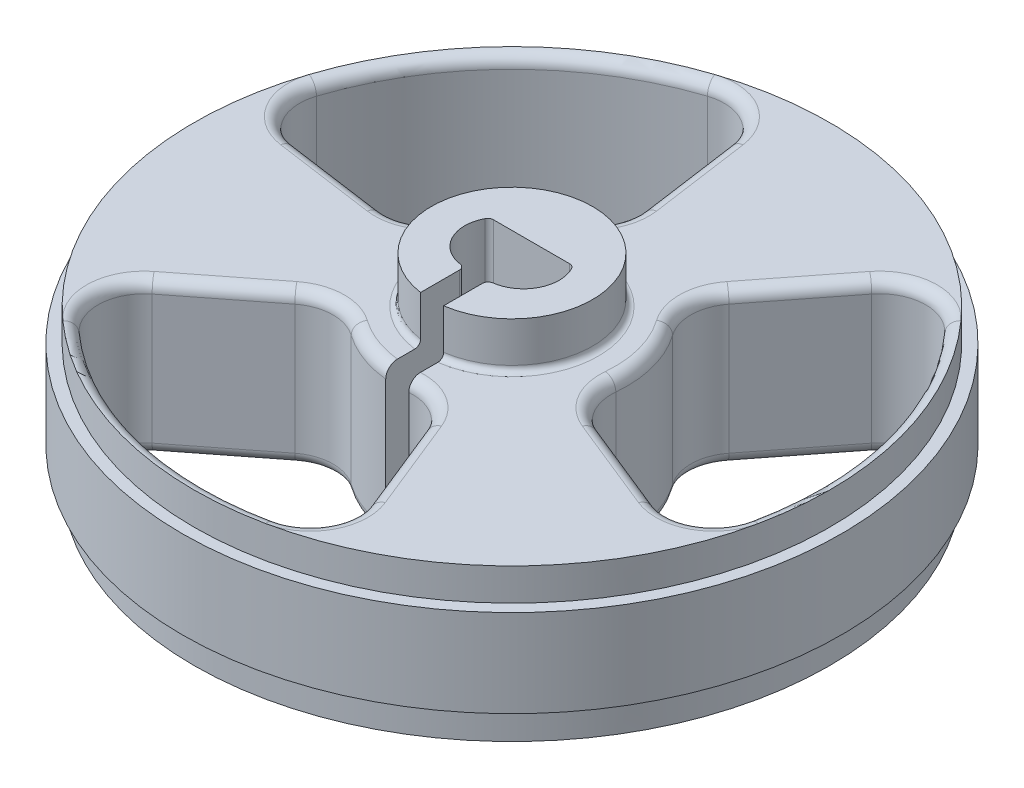
SolidWorks part; units mm, degrees
material "Nylon 101"
ref_plane "Front" through (0, 0, 0) normal (0, 0, 1) x (1, 0, 0)
ref_plane "Top" through (0, 0, 0) normal (0, 1, 0) x (1, 0, 0)
ref_plane "Right" through (0, 0, 0) normal (1, 0, 0) x (0, 0, -1)
sketch "Sketch1" plane through (0, 0, 0) normal (1, 0, 0) x (0, 0, -1)
  line L0 (0, 7.6229) -> (0, -6.4854) construction
  line L1 (0, -4.3) -> (13.8, -4.3)
  line L2 (13.8, -4.3) -> (13.8, -2.9)
  line L3 (13.8, -2.9) -> (14.3, -2.9)
  line L4 (14.3, -2.9) -> (14.3, 0.9)
  line L5 (14.3, 0.9) -> (13.8, 0.9)
  line L6 (13.8, 0.9) -> (13.8, 2.3)
  line L7 (13.8, 2.3) -> (3.5, 2.3)
  line L8 (3.5, 2.3) -> (3.5, 4.3)
  line L9 (3.5, 4.3) -> (0, 4.3)
  line L10 (0, -4.3) -> (0, 4.3)
  point P14 (0, 0)
  dimension "D1" = 6.6
  dimension "D2" = 3.8
  dimension "D3" = 7
  dimension "D4" = 8.6
  dimension "D5" = 14.3
  dimension "D6" = 0.5
revolve "Revolve1" add sketch "Sketch1" angle 360 about L0 other way angle 360
sketch "Sketch2" plane through (0, 2.3, 0) normal (0, 1, 0) x (1, 0, 0)
  line L0 (0, 22.4874) -> (0, -21.7034) construction
  line L1 (-16.3723, 0) -> (20.3716, 0) construction
  line L2 (-1.851, 13.1706) -> (-0.6959, 4.9513)
  line L3 (-13.1706, 1.851) -> (-4.9513, 0.6959)
  arc A1 (-13.1706, 1.851) -> (-1.851, 13.1706) centre (0, 0) cw
  circle A2 centre (0, 0) radius 5
  arc A3 (-0.6959, 4.9513) -> (-4.9513, 0.6959) centre (0, 0) ccw
  circle A4 centre (0, 0) radius 13.8 construction
  dimension "D2" = 0.5
  dimension "D3" = 8
  dimension "D4" = 8
  dimension "D1" = 1.5
extrude "Cut-Extrude1" cut sketch "Sketch2" against normal through all
fillet "Fillet1" radius 2 4 edges at (-4.9513, -1, -0.6959) (-0.6959, -1, -4.9513) (-13.1706, -1, -1.851) (-1.851, -1, -13.1706)
fillet "Fillet2" radius 0.5 16 edges at (-12.4329, 2.3, -2.4714) (-9.4045, 2.3, -9.4045) (-2.4714, 2.3, -12.4329) (-1.2407, 2.3, -8.8281) (-1.1598, 2.3, -5.4042) (-3.5355, 2.3, -3.5355) (-5.4042, 2.3, -1.1598) (-8.8281, 2.3, -1.2407) (-1.1598, -4.3, -5.4042) (-3.5355, -4.3, -3.5355) (-5.4042, -4.3, -1.1598) (-8.8281, -4.3, -1.2407) (-12.4329, -4.3, -2.4714) (-9.4045, -4.3, -9.4045) (-2.4714, -4.3, -12.4329) (-1.2407, -4.3, -8.8281)
ref_axis "Axis1" through (0, 50, 0) along (0, -1, 0)
pattern_circular "CirPattern1" count 3 over 360 about axis through (0, 50, 0) along (0, -1, 0) of "Cut-Extrude1", "Fillet1", "Fillet2"
sketch "Sketch3" plane through (0, 4.3, 0) normal (0, 1, 0) x (1, 0, 0)
  line L0 (0, 0) -> (0, 1.7) construction
  line L1 (-0.5, -5.55) -> (-0.5, -1.55)
  line L2 (-1.7961, 0.85) -> (1.7961, 0.85)
  line L3 (0.5, -5.55) -> (0.5, -1.55)
  line L5 (-0.5, -5.55) -> (0.5, -5.55)
  arc A0 (-2.8963, -4.0757) -> (0.4704, -4.9778) centre (0, 0) ccw construction
  arc A1 (-2.8963, -4.0757) -> (0.4704, -4.9778) centre (0, 0) ccw construction
  arc A2 (-0.5, -1.55) -> (-1.7961, 0.85) centre (-0.5, 0) cw
  arc A3 (0.5, -1.55) -> (1.7961, 0.85) centre (0.5, 0) ccw
  point P15 (0, 0.85)
  dimension "D2" = 1.55
  dimension "D1" = 2.4
  dimension "D3" = 0.5
  dimension "D4" = 4
  dimension "D5" = 0.5
extrude "Cut-Extrude3" cut sketch "Sketch3" against normal through all
fillet "Fillet3" radius 0.25 4 edges at (0.5, 0, 1.55) (-0.5, 0, 1.55) (-1.7961, 0, -0.85) (1.7961, 0, -0.85)
fillet "Fillet4" radius 0.25 1 edges at (0, 2.3, -3.5)
